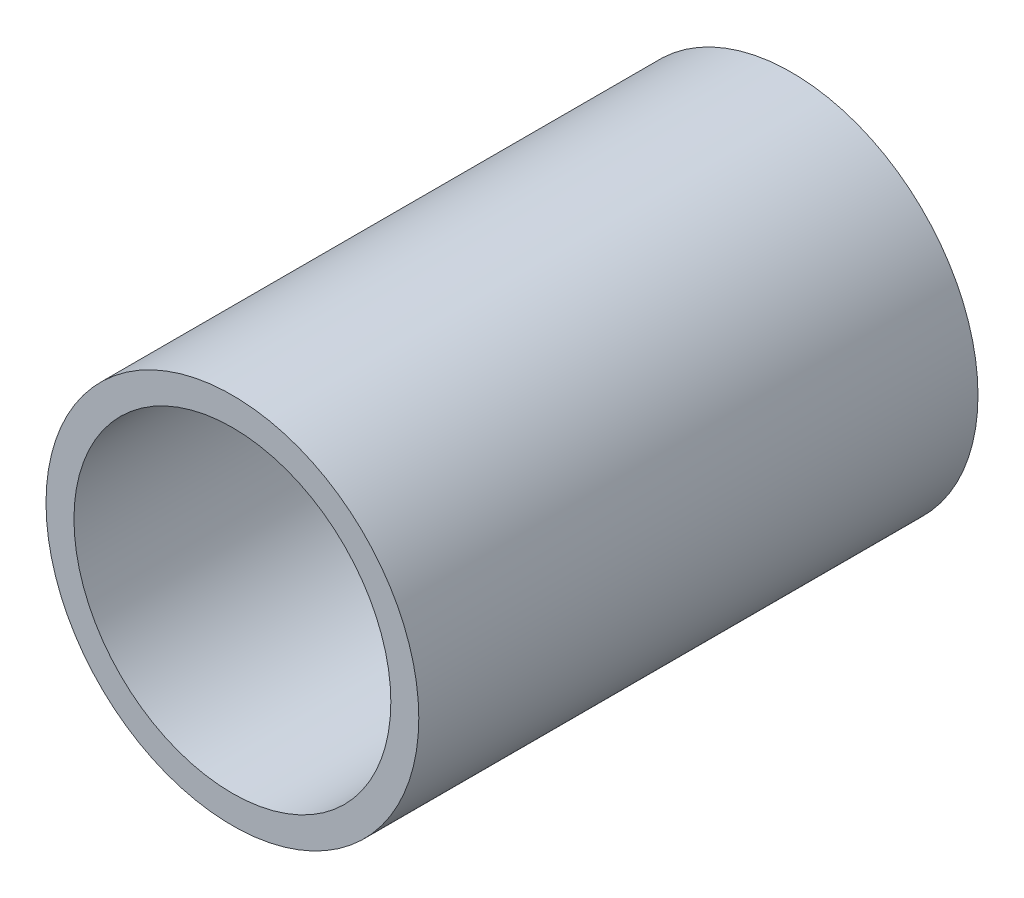
SolidWorks part; units mm, degrees
ref_plane "Front Plane" through (0, 0, 0) normal (0, 0, 1) x (1, 0, 0)
ref_plane "Top Plane" through (0, 0, 0) normal (0, 1, 0) x (1, 0, 0)
ref_plane "Right Plane" through (0, 0, 0) normal (1, 0, 0) x (0, 0, -1)
sketch "Sketch1" plane through (0, 0, 0) normal (0, 0, 1) x (1, 0, 0)
  circle A0 centre (0, 0) radius 100
  dimension "D1" = 200
extrude "Boss-Extrude1" add sketch "Sketch1" along normal blind 150 and the other way blind 150
sketch "Sketch2" plane through (0, 0, 150) normal (0, 0, 1) x (1, 0, 0)
  circle A0 centre (0, 0) radius 85
  dimension "D1" = 170
extrude "Cut-Extrude1" cut sketch "Sketch2" against normal blind 330
